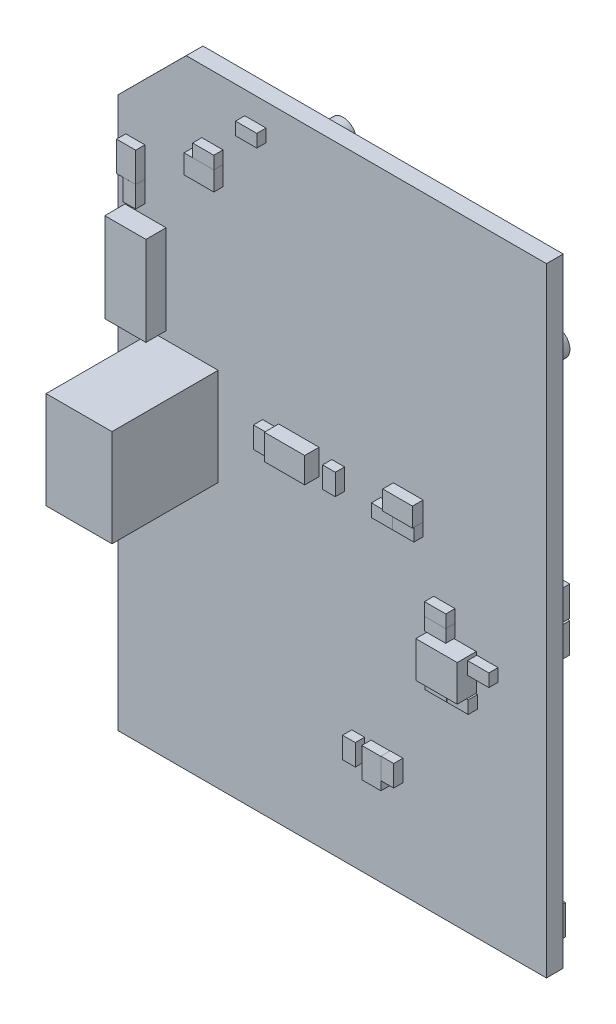
SolidWorks part; units mm, degrees
ref_plane "Plan de face" through (0, 0, 0) normal (0, 0, 1) x (1, 0, 0)
ref_plane "Plan de dessus" through (0, 0, 0) normal (0, 1, 0) x (1, 0, 0)
ref_plane "Plan de droite" through (0, 0, 0) normal (1, 0, 0) x (0, 0, -1)
sketch "Esquisse1" plane through (0, 0, 0) normal (0, 0, 1) x (1, 0, 0)
  line L0 (0, 0) -> (40.32, 0)
  line L1 (40.32, 0) -> (40.32, 58.24)
  line L2 (40.32, 58.24) -> (6.406, 58.24)
  line L3 (6.406, 58.24) -> (0, 51.854)
  line L4 (0, 51.854) -> (0, 0)
extrude "BOARD" add sketch "Esquisse1" along normal blind 1.5748 separate body
ref_plane "Plan1" through (0, 0, 1.5748) normal (0, 0, 1) x (1, 0, 0)
sketch "Esquisse2" plane through (0, 0, 0) normal (0, 0, 1) x (1, 0, 0)
  circle A0 centre (32.2039, 48.279) radius 1.25
extrude "TMR16-1" add sketch "Esquisse2" against normal blind 2.5 separate body
sketch "Esquisse3" plane through (0, 0, 0) normal (0, 0, 1) x (1, 0, 0)
  line L0 (24.4727, 4.7082) -> (27.2727, 4.7082)
  line L1 (27.2727, 4.7082) -> (27.2727, 2.9082)
  line L2 (27.2727, 2.9082) -> (24.4727, 2.9082)
  line L3 (24.4727, 2.9082) -> (24.4727, 4.7082)
extrude "C0603-1" add sketch "Esquisse3" against normal blind 0.87 separate body
sketch "Esquisse4" plane through (0, 0, 0) normal (0, 0, 1) x (1, 0, 0)
  line L0 (21.4089, 41.8009) -> (21.4089, 44.6009)
  line L1 (21.4089, 44.6009) -> (23.2089, 44.6009)
  line L2 (23.2089, 44.6009) -> (23.2089, 41.8009)
  line L3 (23.2089, 41.8009) -> (21.4089, 41.8009)
extrude "R0603-1" add sketch "Esquisse4" against normal blind 0.87 separate body
sketch "Esquisse5" plane through (0, 0, 1.5748) normal (0, 0, 1) x (1, 0, 0)
  line L0 (18.9097, 32.5678) -> (15.1097, 32.5678)
  line L1 (15.1097, 32.5678) -> (15.1097, 30.1678)
  line L2 (15.1097, 30.1678) -> (18.9097, 30.1678)
  line L3 (18.9097, 30.1678) -> (18.9097, 32.5678)
extrude "C0805-1" add sketch "Esquisse5" along normal blind 1.35 separate body
sketch "Esquisse6" plane through (0, 0, 0) normal (0, 0, 1) x (1, 0, 0)
  line L0 (12.7187, 47.5247) -> (12.7187, 44.7247)
  line L1 (12.7187, 44.7247) -> (10.9187, 44.7247)
  line L2 (10.9187, 44.7247) -> (10.9187, 47.5247)
  line L3 (10.9187, 47.5247) -> (12.7187, 47.5247)
extrude "R0603-2" add sketch "Esquisse6" against normal blind 0.87 separate body
sketch "Esquisse7" plane through (0, 0, 1.5748) normal (0, 0, 1) x (1, 0, 0)
  line L0 (9.4166, 24.9432) -> (9.4166, 34.0932)
  line L1 (9.4166, 34.0932) -> (3.2166, 34.0932)
  line L2 (3.2166, 34.0932) -> (3.2166, 24.9432)
  line L3 (3.2166, 24.9432) -> (9.4166, 24.9432)
extrude "B2B-PH-SM4-TB-1" add sketch "Esquisse7" along normal blind 10 separate body
sketch "Esquisse8" plane through (0, 0, 0) normal (0, 0, 1) x (1, 0, 0)
  line L0 (17.22, 23.0445) -> (14.42, 23.0445)
  line L1 (14.42, 23.0445) -> (14.42, 24.8445)
  line L2 (14.42, 24.8445) -> (17.22, 24.8445)
  line L3 (17.22, 24.8445) -> (17.22, 23.0445)
extrude "C0603-2" add sketch "Esquisse8" against normal blind 0.87 separate body
sketch "Esquisse9" plane through (0, 0, 0) normal (0, 0, 1) x (1, 0, 0)
  line L0 (9.9677, 30.5174) -> (9.9677, 32.5174)
  line L1 (9.9677, 32.5174) -> (11.1677, 32.5174)
  line L2 (11.1677, 32.5174) -> (11.1677, 30.5174)
  line L3 (11.1677, 30.5174) -> (9.9677, 30.5174)
extrude "C0402-1" add sketch "Esquisse9" against normal blind 0.87 separate body
sketch "Esquisse10" plane through (0, 0, 0) normal (0, 0, 1) x (1, 0, 0)
  line L0 (18.0259, 36.7794) -> (18.0259, 34.7794)
  line L1 (18.0259, 34.7794) -> (16.8259, 34.7794)
  line L2 (16.8259, 34.7794) -> (16.8259, 36.7794)
  line L3 (16.8259, 36.7794) -> (18.0259, 36.7794)
extrude "C0402-2" add sketch "Esquisse10" against normal blind 0.87 separate body
sketch "Esquisse11" plane through (0, 0, 0) normal (0, 0, 1) x (1, 0, 0)
  line L0 (36.5132, 3.569) -> (36.5132, 1.569)
  line L1 (36.5132, 1.569) -> (35.3132, 1.569)
  line L2 (35.3132, 1.569) -> (35.3132, 3.569)
  line L3 (35.3132, 3.569) -> (36.5132, 3.569)
extrude "C0402-3" add sketch "Esquisse11" against normal blind 0.87 separate body
sketch "Esquisse12" plane through (0, 0, 0) normal (0, 0, 1) x (1, 0, 0)
  line L0 (31.1602, 39.1238) -> (31.1602, 41.9238)
  line L1 (31.1602, 41.9238) -> (32.9602, 41.9238)
  line L2 (32.9602, 41.9238) -> (32.9602, 39.1238)
  line L3 (32.9602, 39.1238) -> (31.1602, 39.1238)
extrude "R0603-3" add sketch "Esquisse12" against normal blind 0.87 separate body
sketch "Esquisse13" plane through (0, 0, 0) normal (0, 0, 1) x (1, 0, 0)
  line L0 (23.2126, 47.4009) -> (23.2126, 44.6009)
  line L1 (23.2126, 44.6009) -> (21.4126, 44.6009)
  line L2 (21.4126, 44.6009) -> (21.4126, 47.4009)
  line L3 (21.4126, 47.4009) -> (23.2126, 47.4009)
extrude "R0603-4" add sketch "Esquisse13" against normal blind 0.87 separate body
sketch "Esquisse14" plane through (0, 0, 1.5748) normal (0, 0, 1) x (1, 0, 0)
  line L0 (0.64, 43.2631) -> (0.64, 34.8631)
  line L1 (0.64, 34.8631) -> (4.5139, 34.8631)
  line L2 (4.5139, 34.8631) -> (4.5139, 43.2631)
  line L3 (4.5139, 43.2631) -> (0.64, 43.2631)
extrude "PCM12SMTR-1" add sketch "Esquisse14" along normal blind 1.9 separate body
sketch "Esquisse17" plane through (0, 0, 0) normal (0, 0, 1) x (1, 0, 0)
  line L0 (26.3939, 26.7629) -> (26.3939, 24.7629)
  line L1 (26.3939, 24.7629) -> (25.1939, 24.7629)
  line L2 (25.1939, 24.7629) -> (25.1939, 26.7629)
  line L3 (25.1939, 26.7629) -> (26.3939, 26.7629)
extrude "C0402-4" add sketch "Esquisse17" against normal blind 0.87 separate body
sketch "Esquisse18" plane through (0, 0, 0) normal (0, 0, 1) x (1, 0, 0)
  line L0 (31.1409, 11.2779) -> (35.3409, 11.2779)
  line L1 (35.3409, 11.2779) -> (35.3409, 8.7779)
  line L2 (35.3409, 8.7779) -> (31.1409, 8.7779)
  line L3 (31.1409, 8.7779) -> (31.1409, 11.2779)
extrude "FC135-1" add sketch "Esquisse18" against normal blind 0.8 separate body
sketch "Esquisse19" plane through (0, 0, 0) normal (0, 0, 1) x (1, 0, 0)
  line L0 (37.8323, 19.2239) -> (35.0323, 19.2239)
  line L1 (35.0323, 19.2239) -> (35.0323, 21.0239)
  line L2 (35.0323, 21.0239) -> (37.8323, 21.0239)
  line L3 (37.8323, 21.0239) -> (37.8323, 19.2239)
extrude "C0603-3" add sketch "Esquisse19" against normal blind 0.87 separate body
sketch "Esquisse20" plane through (0, 0, 1.5748) normal (0, 0, 1) x (1, 0, 0)
  line L0 (31.8247, 18.665) -> (33.8247, 18.665)
  line L1 (33.8247, 18.665) -> (33.8247, 19.865)
  line L2 (33.8247, 19.865) -> (31.8247, 19.865)
  line L3 (31.8247, 19.865) -> (31.8247, 18.665)
extrude "C0402-5" add sketch "Esquisse20" along normal blind 0.87 separate body
sketch "Esquisse21" plane through (0, 0, 0) normal (0, 0, 1) x (1, 0, 0)
  line L0 (16.4144, 19.928) -> (16.4144, 17.928)
  line L1 (16.4144, 17.928) -> (15.2144, 17.928)
  line L2 (15.2144, 17.928) -> (15.2144, 19.928)
  line L3 (15.2144, 19.928) -> (16.4144, 19.928)
extrude "R0402-1" add sketch "Esquisse21" against normal blind 0.87 separate body
sketch "Esquisse22" plane through (0, 0, 1.5748) normal (0, 0, 1) x (1, 0, 0)
  line L0 (23.1938, 9.067) -> (23.1938, 11.067)
  line L1 (23.1938, 11.067) -> (21.9938, 11.067)
  line L2 (21.9938, 11.067) -> (21.9938, 9.067)
  line L3 (21.9938, 9.067) -> (23.1938, 9.067)
extrude "R0402-2" add sketch "Esquisse22" along normal blind 0.87 separate body
sketch "Esquisse24" plane through (0, 0, 0) normal (0, 0, 1) x (1, 0, 0)
  line L0 (16.8284, 26.8617) -> (16.8284, 24.8617)
  line L1 (16.8284, 24.8617) -> (15.6284, 24.8617)
  line L2 (15.6284, 24.8617) -> (15.6284, 26.8617)
  line L3 (15.6284, 26.8617) -> (16.8284, 26.8617)
extrude "C0402-6" add sketch "Esquisse24" against normal blind 0.87 separate body
sketch "Esquisse25" plane through (0, 0, 1.5748) normal (0, 0, 1) x (1, 0, 0)
  line L0 (31.7718, 19.8619) -> (29.7718, 19.8619)
  line L1 (29.7718, 19.8619) -> (29.7718, 18.6619)
  line L2 (29.7718, 18.6619) -> (31.7718, 18.6619)
  line L3 (31.7718, 18.6619) -> (31.7718, 19.8619)
extrude "C0402-7" add sketch "Esquisse25" along normal blind 0.87 separate body
sketch "Esquisse26" plane through (0, 0, 0) normal (0, 0, 1) x (1, 0, 0)
  line L0 (25.1939, 26.7658) -> (25.1939, 23.9658)
  line L1 (25.1939, 23.9658) -> (23.3939, 23.9658)
  line L2 (23.3939, 23.9658) -> (23.3939, 26.7658)
  line L3 (23.3939, 26.7658) -> (25.1939, 26.7658)
extrude "C0603-4" add sketch "Esquisse26" against normal blind 0.87 separate body
sketch "Esquisse27" plane through (0, 0, 1.5748) normal (0, 0, 1) x (1, 0, 0)
  line L0 (7.8734, 51.0902) -> (9.8734, 51.0902)
  line L1 (9.8734, 51.0902) -> (9.8734, 52.2902)
  line L2 (9.8734, 52.2902) -> (7.8734, 52.2902)
  line L3 (7.8734, 52.2902) -> (7.8734, 51.0902)
extrude "C0402-8" add sketch "Esquisse27" along normal blind 0.87 separate body
sketch "Esquisse28" plane through (0, 0, 0) normal (0, 0, 1) x (1, 0, 0)
  line L0 (29.9409, 8.7816) -> (29.9409, 10.7816)
  line L1 (29.9409, 10.7816) -> (31.1409, 10.7816)
  line L2 (31.1409, 10.7816) -> (31.1409, 8.7816)
  line L3 (31.1409, 8.7816) -> (29.9409, 8.7816)
extrude "C0402-9" add sketch "Esquisse28" against normal blind 0.87 separate body
sketch "Esquisse29" plane through (0, 0, 0) normal (0, 0, 1) x (1, 0, 0)
  line L0 (30.2532, 33.9315) -> (33.0532, 33.9315)
  line L1 (33.0532, 33.9315) -> (33.0532, 32.1315)
  line L2 (33.0532, 32.1315) -> (30.2532, 32.1315)
  line L3 (30.2532, 32.1315) -> (30.2532, 33.9315)
extrude "R0603-5" add sketch "Esquisse29" against normal blind 0.87 separate body
sketch "Esquisse30" plane through (0, 0, 0) normal (0, 0, 1) x (1, 0, 0)
  circle A0 centre (37.2015, 48.2753) radius 1.25
extrude "TMR16-2" add sketch "Esquisse30" against normal blind 2.5 separate body
sketch "Esquisse31" plane through (0, 0, 0) normal (0, 0, 1) x (1, 0, 0)
  line L0 (30.266, 27.6789) -> (30.266, 29.6789)
  line L1 (30.266, 29.6789) -> (31.466, 29.6789)
  line L2 (31.466, 29.6789) -> (31.466, 27.6789)
  line L3 (31.466, 27.6789) -> (30.266, 27.6789)
extrude "C0402-10" add sketch "Esquisse31" against normal blind 0.87 separate body
sketch "Esquisse33" plane through (0, 0, 0) normal (0, 0, 1) x (1, 0, 0)
  line L0 (33.1436, 12.4818) -> (35.1436, 12.4818)
  line L1 (35.1436, 12.4818) -> (35.1436, 11.2818)
  line L2 (35.1436, 11.2818) -> (33.1436, 11.2818)
  line L3 (33.1436, 11.2818) -> (33.1436, 12.4818)
extrude "C0402-11" add sketch "Esquisse33" against normal blind 0.87 separate body
sketch "Esquisse34" plane through (0, 0, 0) normal (0, 0, 1) x (1, 0, 0)
  line L0 (38.6703, 42.6598) -> (38.6703, 40.6598)
  line L1 (38.6703, 40.6598) -> (37.4703, 40.6598)
  line L2 (37.4703, 40.6598) -> (37.4703, 42.6598)
  line L3 (37.4703, 42.6598) -> (38.6703, 42.6598)
extrude "C0402-12" add sketch "Esquisse34" against normal blind 0.87 separate body
sketch "Esquisse36" plane through (0, 0, 0) normal (0, 0, 1) x (1, 0, 0)
  line L0 (38.6602, 38.2995) -> (38.6602, 36.2995)
  line L1 (38.6602, 36.2995) -> (37.4602, 36.2995)
  line L2 (37.4602, 36.2995) -> (37.4602, 38.2995)
  line L3 (37.4602, 38.2995) -> (38.6602, 38.2995)
extrude "R0402-3" add sketch "Esquisse36" against normal blind 0.87 separate body
sketch "Esquisse37" plane through (0, 0, 0) normal (0, 0, 1) x (1, 0, 0)
  line L0 (23.2036, 40.9713) -> (23.2036, 38.9713)
  line L1 (23.2036, 38.9713) -> (22.0036, 38.9713)
  line L2 (22.0036, 38.9713) -> (22.0036, 40.9713)
  line L3 (22.0036, 40.9713) -> (23.2036, 40.9713)
extrude "R0402-4" add sketch "Esquisse37" against normal blind 0.87 separate body
sketch "Esquisse38" plane through (0, 0, 1.5748) normal (0, 0, 1) x (1, 0, 0)
  line L0 (25.907, 31.3651) -> (28.707, 31.3651)
  line L1 (28.707, 31.3651) -> (28.707, 33.1651)
  line L2 (28.707, 33.1651) -> (25.907, 33.1651)
  line L3 (25.907, 33.1651) -> (25.907, 31.3651)
extrude "D0603-1" add sketch "Esquisse38" along normal blind 1 separate body
sketch "Esquisse39" plane through (0, 0, 0) normal (0, 0, 1) x (1, 0, 0)
  line L0 (33.3683, 1.6523) -> (34.3683, 1.6523)
  line L1 (34.3683, 1.6523) -> (34.3683, 0.6523)
  line L2 (34.3683, 0.6523) -> (33.3683, 0.6523)
  line L3 (33.3683, 0.6523) -> (33.3683, 1.6523)
extrude "PAD_1x1-1" add sketch "Esquisse39" against normal blind 2.54 separate body
sketch "Esquisse40" plane through (0, 0, 1.5748) normal (0, 0, 1) x (1, 0, 0)
  line L0 (33.7636, 21.8308) -> (35.7636, 21.8308)
  line L1 (35.7636, 21.8308) -> (35.7636, 23.0308)
  line L2 (35.7636, 23.0308) -> (33.7636, 23.0308)
  line L3 (33.7636, 23.0308) -> (33.7636, 21.8308)
extrude "C0402-13" add sketch "Esquisse40" along normal blind 0.87 separate body
sketch "Esquisse41" plane through (0, 0, 1.5748) normal (0, 0, 1) x (1, 0, 0)
  line L0 (26.7069, 30.1651) -> (28.7069, 30.1651)
  line L1 (28.7069, 30.1651) -> (28.7069, 31.3651)
  line L2 (28.7069, 31.3651) -> (26.7069, 31.3651)
  line L3 (26.7069, 31.3651) -> (26.7069, 30.1651)
extrude "R0402-5" add sketch "Esquisse41" along normal blind 0.87 separate body
sketch "Esquisse42" plane through (0, 0, 1.5748) normal (0, 0, 1) x (1, 0, 0)
  line L0 (31.7099, 24.6143) -> (29.7099, 24.6143)
  line L1 (29.7099, 24.6143) -> (29.7099, 23.4143)
  line L2 (29.7099, 23.4143) -> (31.7099, 23.4143)
  line L3 (31.7099, 23.4143) -> (31.7099, 24.6143)
extrude "C0402-14" add sketch "Esquisse42" along normal blind 0.87 separate body
sketch "Esquisse43" plane through (0, 0, 0) normal (0, 0, 1) x (1, 0, 0)
  line L0 (17.2288, 45.591) -> (17.2288, 47.591)
  line L1 (17.2288, 47.591) -> (18.4288, 47.591)
  line L2 (18.4288, 47.591) -> (18.4288, 45.591)
  line L3 (18.4288, 45.591) -> (17.2288, 45.591)
extrude "R0402-6" add sketch "Esquisse43" against normal blind 0.87 separate body
sketch "Esquisse44" plane through (0, 0, 1.5748) normal (0, 0, 1) x (1, 0, 0)
  line L0 (0.7203, 49.0243) -> (0.7203, 46.2243)
  line L1 (0.7203, 46.2243) -> (2.5203, 46.2243)
  line L2 (2.5203, 46.2243) -> (2.5203, 49.0243)
  line L3 (2.5203, 49.0243) -> (0.7203, 49.0243)
extrude "C0603-5" add sketch "Esquisse44" along normal blind 0.87 separate body
sketch "Esquisse45" plane through (0, 0, 0) normal (0, 0, 1) x (1, 0, 0)
  line L0 (23.2977, 35.9913) -> (26.0977, 35.9913)
  line L1 (26.0977, 35.9913) -> (26.0977, 34.1913)
  line L2 (26.0977, 34.1913) -> (23.2977, 34.1913)
  line L3 (23.2977, 34.1913) -> (23.2977, 35.9913)
extrude "R0603-6" add sketch "Esquisse45" against normal blind 0.87 separate body
sketch "Esquisse46" plane through (0, 0, 0) normal (0, 0, 1) x (1, 0, 0)
  line L0 (10.0607, 36.7556) -> (12.8607, 36.7556)
  line L1 (12.8607, 36.7556) -> (12.8607, 34.9556)
  line L2 (12.8607, 34.9556) -> (10.0607, 34.9556)
  line L3 (10.0607, 34.9556) -> (10.0607, 36.7556)
extrude "R0603-7" add sketch "Esquisse46" against normal blind 0.87 separate body
sketch "Esquisse47" plane through (0, 0, 0) normal (0, 0, 1) x (1, 0, 0)
  line L0 (28.9167, 40.9735) -> (28.9167, 38.9735)
  line L1 (28.9167, 38.9735) -> (27.7167, 38.9735)
  line L2 (27.7167, 38.9735) -> (27.7167, 40.9735)
  line L3 (27.7167, 40.9735) -> (28.9167, 40.9735)
extrude "R0402-7" add sketch "Esquisse47" against normal blind 0.87 separate body
sketch "Esquisse48" plane through (0, 0, 0) normal (0, 0, 1) x (1, 0, 0)
  line L0 (28.4582, 27.7214) -> (28.4582, 30.5214)
  line L1 (28.4582, 30.5214) -> (30.2582, 30.5214)
  line L2 (30.2582, 30.5214) -> (30.2582, 27.7214)
  line L3 (30.2582, 27.7214) -> (28.4582, 27.7214)
extrude "C0603-6" add sketch "Esquisse48" against normal blind 0.87 separate body
sketch "Esquisse49" plane through (0, 0, 0) normal (0, 0, 1) x (1, 0, 0)
  line L0 (18.3486, 51.2303) -> (18.3486, 54.0303)
  line L1 (18.3486, 54.0303) -> (20.1486, 54.0303)
  line L2 (20.1486, 54.0303) -> (20.1486, 51.2303)
  line L3 (20.1486, 51.2303) -> (18.3486, 51.2303)
extrude "C0603-7" add sketch "Esquisse49" against normal blind 0.87 separate body
sketch "Esquisse52" plane through (0, 0, 0) normal (0, 0, 1) x (1, 0, 0)
  line L0 (28.4532, 30.5214) -> (28.4532, 33.3214)
  line L1 (28.4532, 33.3214) -> (30.2532, 33.3214)
  line L2 (30.2532, 33.3214) -> (30.2532, 30.5214)
  line L3 (30.2532, 30.5214) -> (28.4532, 30.5214)
extrude "C0603-8" add sketch "Esquisse52" against normal blind 0.87 separate body
sketch "Esquisse53" plane through (0, 0, 0) normal (0, 0, 1) x (1, 0, 0)
  line L0 (12.6415, 15.1419) -> (12.6415, 13.1419)
  line L1 (12.6415, 13.1419) -> (11.4415, 13.1419)
  line L2 (11.4415, 13.1419) -> (11.4415, 15.1419)
  line L3 (11.4415, 15.1419) -> (12.6415, 15.1419)
extrude "C0402-15" add sketch "Esquisse53" against normal blind 0.87 separate body
sketch "Esquisse54" plane through (0, 0, 0) normal (0, 0, 1) x (1, 0, 0)
  line L0 (14.428, 17.8103) -> (16.428, 17.8103)
  line L1 (16.428, 17.8103) -> (16.428, 16.6103)
  line L2 (16.428, 16.6103) -> (14.428, 16.6103)
  line L3 (14.428, 16.6103) -> (14.428, 17.8103)
extrude "C0402-16" add sketch "Esquisse54" against normal blind 0.87 separate body
sketch "Esquisse55" plane through (0, 0, 1.5748) normal (0, 0, 1) x (1, 0, 0)
  line L0 (33.7164, 19.9169) -> (33.7164, 23.3169)
  line L1 (33.7164, 23.3169) -> (29.8164, 23.3169)
  line L2 (29.8164, 23.3169) -> (29.8164, 19.9169)
  line L3 (29.8164, 19.9169) -> (33.7164, 19.9169)
extrude "NX2520-1" add sketch "Esquisse55" along normal blind 1.8 separate body
sketch "Esquisse56" plane through (0, 0, 0) normal (0, 0, 1) x (1, 0, 0)
  line L0 (37.6786, 21.5996) -> (35.6786, 21.5996)
  line L1 (35.6786, 21.5996) -> (35.6786, 22.7996)
  line L2 (35.6786, 22.7996) -> (37.6786, 22.7996)
  line L3 (37.6786, 22.7996) -> (37.6786, 21.5996)
extrude "C0402-17" add sketch "Esquisse56" against normal blind 0.87 separate body
sketch "Esquisse57" plane through (0, 0, 0) normal (0, 0, 1) x (1, 0, 0)
  line L0 (17.9677, 27.8144) -> (17.9677, 30.6144)
  line L1 (17.9677, 30.6144) -> (19.7677, 30.6144)
  line L2 (19.7677, 30.6144) -> (19.7677, 27.8144)
  line L3 (19.7677, 27.8144) -> (17.9677, 27.8144)
extrude "C0603-9" add sketch "Esquisse57" against normal blind 0.87 separate body
sketch "Esquisse59" plane through (0, 0, 0) normal (0, 0, 1) x (1, 0, 0)
  line L0 (18.4233, 41.0792) -> (18.4233, 39.0792)
  line L1 (18.4233, 39.0792) -> (17.2233, 39.0792)
  line L2 (17.2233, 39.0792) -> (17.2233, 41.0792)
  line L3 (17.2233, 41.0792) -> (18.4233, 41.0792)
extrude "R0402-8" add sketch "Esquisse59" against normal blind 0.87 separate body
sketch "Esquisse60" plane through (0, 0, 0) normal (0, 0, 1) x (1, 0, 0)
  line L0 (28.5034, 36.6137) -> (28.5034, 34.6137)
  line L1 (28.5034, 34.6137) -> (27.3034, 34.6137)
  line L2 (27.3034, 34.6137) -> (27.3034, 36.6137)
  line L3 (27.3034, 36.6137) -> (28.5034, 36.6137)
extrude "C0402-18" add sketch "Esquisse60" against normal blind 0.87 separate body
sketch "Esquisse61" plane through (0, 0, 0) normal (0, 0, 1) x (1, 0, 0)
  line L0 (28.4922, 4.2513) -> (28.4922, 2.2513)
  line L1 (28.4922, 2.2513) -> (27.2922, 2.2513)
  line L2 (27.2922, 2.2513) -> (27.2922, 4.2513)
  line L3 (27.2922, 4.2513) -> (28.4922, 4.2513)
extrude "C0402-19" add sketch "Esquisse61" against normal blind 0.87 separate body
sketch "Esquisse63" plane through (0, 0, 0) normal (0, 0, 1) x (1, 0, 0)
  line L0 (12.8704, 36.123) -> (15.6704, 36.123)
  line L1 (15.6704, 36.123) -> (15.6704, 34.323)
  line L2 (15.6704, 34.323) -> (12.8704, 34.323)
  line L3 (12.8704, 34.323) -> (12.8704, 36.123)
extrude "R0603-8" add sketch "Esquisse63" against normal blind 0.87 separate body
sketch "Esquisse64" plane through (0, 0, 0) normal (0, 0, 1) x (1, 0, 0)
  line L0 (20.0201, 20.1616) -> (18.0201, 20.1616)
  line L1 (18.0201, 20.1616) -> (18.0201, 21.3616)
  line L2 (18.0201, 21.3616) -> (20.0201, 21.3616)
  line L3 (20.0201, 21.3616) -> (20.0201, 20.1616)
extrude "C0402-20" add sketch "Esquisse64" against normal blind 0.87 separate body
sketch "Esquisse65" plane through (0, 0, 1.5748) normal (0, 0, 1) x (1, 0, 0)
  line L0 (20.1126, 32.1652) -> (20.1126, 30.1652)
  line L1 (20.1126, 30.1652) -> (21.3126, 30.1652)
  line L2 (21.3126, 30.1652) -> (21.3126, 32.1652)
  line L3 (21.3126, 32.1652) -> (20.1126, 32.1652)
extrude "R0402-9" add sketch "Esquisse65" along normal blind 0.87 separate body
sketch "Esquisse66" plane through (0, 0, 0) normal (0, 0, 1) x (1, 0, 0)
  line L0 (37.4717, 42.6598) -> (37.4717, 44.6598)
  line L1 (37.4717, 44.6598) -> (38.6717, 44.6598)
  line L2 (38.6717, 44.6598) -> (38.6717, 42.6598)
  line L3 (38.6717, 42.6598) -> (37.4717, 42.6598)
extrude "R0402-10" add sketch "Esquisse66" against normal blind 0.87 separate body
sketch "Esquisse69" plane through (0, 0, 0) normal (0, 0, 1) x (1, 0, 0)
  line L0 (31.9877, 1.64) -> (32.9877, 1.64)
  line L1 (32.9877, 1.64) -> (32.9877, 0.64)
  line L2 (32.9877, 0.64) -> (31.9877, 0.64)
  line L3 (31.9877, 0.64) -> (31.9877, 1.64)
extrude "PAD_1x1-2" add sketch "Esquisse69" against normal blind 2.54 separate body
sketch "Esquisse70" plane through (0, 0, 0) normal (0, 0, 1) x (1, 0, 0)
  line L0 (32.9602, 44.7238) -> (32.9602, 41.9238)
  line L1 (32.9602, 41.9238) -> (31.1602, 41.9238)
  line L2 (31.1602, 41.9238) -> (31.1602, 44.7238)
  line L3 (31.1602, 44.7238) -> (32.9602, 44.7238)
extrude "R0603-9" add sketch "Esquisse70" against normal blind 0.87 separate body
sketch "Esquisse72" plane through (0, 0, 0) normal (0, 0, 1) x (1, 0, 0)
  line L0 (37.6897, 22.8247) -> (35.6897, 22.8247)
  line L1 (35.6897, 22.8247) -> (35.6897, 24.0247)
  line L2 (35.6897, 24.0247) -> (37.6897, 24.0247)
  line L3 (37.6897, 24.0247) -> (37.6897, 22.8247)
extrude "C0402-21" add sketch "Esquisse72" against normal blind 0.87 separate body
sketch "Esquisse73" plane through (0, 0, 0) normal (0, 0, 1) x (1, 0, 0)
  line L0 (38.266, 27.9786) -> (38.266, 30.7786)
  line L1 (38.266, 30.7786) -> (40.066, 30.7786)
  line L2 (40.066, 30.7786) -> (40.066, 27.9786)
  line L3 (40.066, 27.9786) -> (38.266, 27.9786)
extrude "C0603-10" add sketch "Esquisse73" against normal blind 0.87 separate body
sketch "Esquisse74" plane through (0, 0, 0) normal (0, 0, 1) x (1, 0, 0)
  line L0 (36.5201, 5.6764) -> (36.5201, 3.6764)
  line L1 (36.5201, 3.6764) -> (35.3201, 3.6764)
  line L2 (35.3201, 3.6764) -> (35.3201, 5.6764)
  line L3 (35.3201, 5.6764) -> (36.5201, 5.6764)
extrude "R0402-11" add sketch "Esquisse74" against normal blind 0.87 separate body
sketch "Esquisse76" plane through (0, 0, 0) normal (0, 0, 1) x (1, 0, 0)
  line L0 (38.266, 24.9805) -> (38.266, 27.7805)
  line L1 (38.266, 27.7805) -> (40.066, 27.7805)
  line L2 (40.066, 27.7805) -> (40.066, 24.9805)
  line L3 (40.066, 24.9805) -> (38.266, 24.9805)
extrude "C0603-11" add sketch "Esquisse76" against normal blind 0.87 separate body
sketch "Esquisse77" plane through (0, 0, 0) normal (0, 0, 1) x (1, 0, 0)
  line L0 (10.7187, 48.7247) -> (12.7187, 48.7247)
  line L1 (12.7187, 48.7247) -> (12.7187, 47.5247)
  line L2 (12.7187, 47.5247) -> (10.7187, 47.5247)
  line L3 (10.7187, 47.5247) -> (10.7187, 48.7247)
extrude "C0402-22" add sketch "Esquisse77" against normal blind 0.87 separate body
sketch "Esquisse78" plane through (0, 0, 0) normal (0, 0, 1) x (1, 0, 0)
  line L0 (18.4288, 45.591) -> (18.4288, 43.591)
  line L1 (18.4288, 43.591) -> (17.2288, 43.591)
  line L2 (17.2288, 43.591) -> (17.2288, 45.591)
  line L3 (17.2288, 45.591) -> (18.4288, 45.591)
extrude "C0402-23" add sketch "Esquisse78" against normal blind 0.87 separate body
sketch "Esquisse80" plane through (0, 0, 0) normal (0, 0, 1) x (1, 0, 0)
  line L0 (39.3369, 4.4834) -> (36.5369, 4.4834)
  line L1 (36.5369, 4.4834) -> (36.5369, 6.2834)
  line L2 (36.5369, 6.2834) -> (39.3369, 6.2834)
  line L3 (39.3369, 6.2834) -> (39.3369, 4.4834)
extrude "R0603-10" add sketch "Esquisse80" against normal blind 0.87 separate body
sketch "Esquisse81" plane through (0, 0, 0) normal (0, 0, 1) x (1, 0, 0)
  circle A0 centre (17.0986, 50.277) radius 1.25
extrude "TMR16-3" add sketch "Esquisse81" against normal blind 2.5 separate body
sketch "Esquisse82" plane through (0, 0, 0) normal (0, 0, 1) x (1, 0, 0)
  line L0 (26.5132, 8.1312) -> (28.5132, 8.1312)
  line L1 (28.5132, 8.1312) -> (28.5132, 6.9312)
  line L2 (28.5132, 6.9312) -> (26.5132, 6.9312)
  line L3 (26.5132, 6.9312) -> (26.5132, 8.1312)
extrude "C0402-24" add sketch "Esquisse82" against normal blind 0.87 separate body
sketch "Esquisse85" plane through (0, 0, 1.5748) normal (0, 0, 1) x (1, 0, 0)
  line L0 (26.808, 9.1651) -> (26.808, 11.1651)
  line L1 (26.808, 11.1651) -> (25.608, 11.1651)
  line L2 (25.608, 11.1651) -> (25.608, 9.1651)
  line L3 (25.608, 9.1651) -> (26.808, 9.1651)
extrude "C0402-25" add sketch "Esquisse85" along normal blind 0.87 separate body
sketch "Esquisse86" plane through (0, 0, 0) normal (0, 0, 1) x (1, 0, 0)
  line L0 (29.7581, 8.8221) -> (26.3581, 8.8221)
  line L1 (26.3581, 8.8221) -> (26.3581, 12.7221)
  line L2 (26.3581, 12.7221) -> (29.7581, 12.7221)
  line L3 (29.7581, 12.7221) -> (29.7581, 8.8221)
extrude "NX2520-2" add sketch "Esquisse86" against normal blind 1.8 separate body
sketch "Esquisse88" plane through (0, 0, 0) normal (0, 0, 1) x (1, 0, 0)
  line L0 (22.7677, 17.3617) -> (22.7677, 20.1617)
  line L1 (22.7677, 20.1617) -> (24.5677, 20.1617)
  line L2 (24.5677, 20.1617) -> (24.5677, 17.3617)
  line L3 (24.5677, 17.3617) -> (22.7677, 17.3617)
extrude "C0603-12" add sketch "Esquisse88" against normal blind 0.87 separate body
sketch "Esquisse89" plane through (0, 0, 0) normal (0, 0, 1) x (1, 0, 0)
  line L0 (33.0532, 33.3221) -> (35.8532, 33.3221)
  line L1 (35.8532, 33.3221) -> (35.8532, 31.5221)
  line L2 (35.8532, 31.5221) -> (33.0532, 31.5221)
  line L3 (33.0532, 31.5221) -> (33.0532, 33.3221)
extrude "R0603-11" add sketch "Esquisse89" against normal blind 0.87 separate body
sketch "Esquisse90" plane through (0, 0, 0) normal (0, 0, 1) x (1, 0, 0)
  line L0 (21.2114, 48.6009) -> (23.2114, 48.6009)
  line L1 (23.2114, 48.6009) -> (23.2114, 47.4009)
  line L2 (23.2114, 47.4009) -> (21.2114, 47.4009)
  line L3 (21.2114, 47.4009) -> (21.2114, 48.6009)
extrude "C0402-26" add sketch "Esquisse90" against normal blind 0.87 separate body
sketch "Esquisse91" plane through (0, 0, 0) normal (0, 0, 1) x (1, 0, 0)
  line L0 (30.9904, 13.5763) -> (30.9904, 11.5763)
  line L1 (30.9904, 11.5763) -> (29.7904, 11.5763)
  line L2 (29.7904, 11.5763) -> (29.7904, 13.5763)
  line L3 (29.7904, 13.5763) -> (30.9904, 13.5763)
extrude "C0402-27" add sketch "Esquisse91" against normal blind 0.87 separate body
sketch "Esquisse92" plane through (0, 0, 1.5748) normal (0, 0, 1) x (1, 0, 0)
  line L0 (26.7052, 31.3651) -> (24.7052, 31.3651)
  line L1 (24.7052, 31.3651) -> (24.7052, 30.1651)
  line L2 (24.7052, 30.1651) -> (26.7052, 30.1651)
  line L3 (26.7052, 30.1651) -> (26.7052, 31.3651)
extrude "C0402-28" add sketch "Esquisse92" along normal blind 0.87 separate body
sketch "Esquisse93" plane through (0, 0, 0) normal (0, 0, 1) x (1, 0, 0)
  line L0 (22.1939, 24.7606) -> (22.1939, 26.7606)
  line L1 (22.1939, 26.7606) -> (23.3939, 26.7606)
  line L2 (23.3939, 26.7606) -> (23.3939, 24.7606)
  line L3 (23.3939, 24.7606) -> (22.1939, 24.7606)
extrude "R0402-12" add sketch "Esquisse93" against normal blind 0.87 separate body
sketch "Esquisse94" plane through (0, 0, 0) normal (0, 0, 1) x (1, 0, 0)
  line L0 (28.9138, 45.487) -> (28.9138, 43.487)
  line L1 (28.9138, 43.487) -> (27.7138, 43.487)
  line L2 (27.7138, 43.487) -> (27.7138, 45.487)
  line L3 (27.7138, 45.487) -> (28.9138, 45.487)
extrude "C0402-29" add sketch "Esquisse94" against normal blind 0.87 separate body
sketch "Esquisse95" plane through (0, 0, 0) normal (0, 0, 1) x (1, 0, 0)
  line L0 (6.8995, 16.8472) -> (10.6995, 16.8472)
  line L1 (10.6995, 16.8472) -> (10.6995, 14.4472)
  line L2 (10.6995, 14.4472) -> (6.8995, 14.4472)
  line L3 (6.8995, 14.4472) -> (6.8995, 16.8472)
extrude "C0805-2" add sketch "Esquisse95" against normal blind 1.35 separate body
sketch "Esquisse96" plane through (0, 0, 0) normal (0, 0, 1) x (1, 0, 0)
  line L0 (20.4914, 36.5874) -> (23.2914, 36.5874)
  line L1 (23.2914, 36.5874) -> (23.2914, 34.7874)
  line L2 (23.2914, 34.7874) -> (20.4914, 34.7874)
  line L3 (20.4914, 34.7874) -> (20.4914, 36.5874)
extrude "R0603-12" add sketch "Esquisse96" against normal blind 0.87 separate body
sketch "Esquisse97" plane through (0, 0, 0) normal (0, 0, 1) x (1, 0, 0)
  line L0 (23.1885, 2.8155) -> (23.1885, 0.8155)
  line L1 (23.1885, 0.8155) -> (21.9885, 0.8155)
  line L2 (21.9885, 0.8155) -> (21.9885, 2.8155)
  line L3 (21.9885, 2.8155) -> (23.1885, 2.8155)
extrude "C0402-30" add sketch "Esquisse97" against normal blind 0.87 separate body
sketch "Esquisse99" plane through (0, 0, 0) normal (0, 0, 1) x (1, 0, 0)
  line L0 (37.7446, 1.672) -> (37.7446, 4.472)
  line L1 (37.7446, 4.472) -> (39.5446, 4.472)
  line L2 (39.5446, 4.472) -> (39.5446, 1.672)
  line L3 (39.5446, 1.672) -> (37.7446, 1.672)
extrude "D0603-2" add sketch "Esquisse99" against normal blind 1 separate body
sketch "Esquisse100" plane through (0, 0, 0) normal (0, 0, 1) x (1, 0, 0)
  line L0 (5.454, 0.254) -> (0.254, 0.254)
  line L1 (0.254, 0.254) -> (0.254, 3.854)
  line L2 (0.254, 3.854) -> (5.454, 3.854)
  line L3 (5.454, 3.854) -> (5.454, 0.254)
extrude "2450AT18A100-1" add sketch "Esquisse100" against normal blind 1.3 separate body
sketch "Esquisse101" plane through (0, 0, 1.5748) normal (0, 0, 1) x (1, 0, 0)
  line L0 (13.6077, 32.1678) -> (13.6077, 30.1678)
  line L1 (13.6077, 30.1678) -> (14.8077, 30.1678)
  line L2 (14.8077, 30.1678) -> (14.8077, 32.1678)
  line L3 (14.8077, 32.1678) -> (13.6077, 32.1678)
extrude "C0402-31" add sketch "Esquisse101" along normal blind 0.87 separate body
sketch "Esquisse102" plane through (0, 0, 0) normal (0, 0, 1) x (1, 0, 0)
  line L0 (10.9187, 41.9247) -> (10.9187, 44.7247)
  line L1 (10.9187, 44.7247) -> (12.7187, 44.7247)
  line L2 (12.7187, 44.7247) -> (12.7187, 41.9247)
  line L3 (12.7187, 41.9247) -> (10.9187, 41.9247)
extrude "R0603-13" add sketch "Esquisse102" against normal blind 0.87 separate body
sketch "Esquisse104" plane through (0, 0, 0) normal (0, 0, 1) x (1, 0, 0)
  circle A0 centre (17.1015, 55.2803) radius 1.25
extrude "TMR16-4" add sketch "Esquisse104" against normal blind 2.5 separate body
sketch "Esquisse105" plane through (0, 0, 0) normal (0, 0, 1) x (1, 0, 0)
  line L0 (15.6284, 26.8629) -> (15.6284, 24.8629)
  line L1 (15.6284, 24.8629) -> (14.4284, 24.8629)
  line L2 (14.4284, 24.8629) -> (14.4284, 26.8629)
  line L3 (14.4284, 26.8629) -> (15.6284, 26.8629)
extrude "C0402-32" add sketch "Esquisse105" against normal blind 0.87 separate body
sketch "Esquisse106" plane through (0, 0, 0) normal (0, 0, 1) x (1, 0, 0)
  line L0 (23.3594, 51.6851) -> (26.1594, 51.6851)
  line L1 (26.1594, 51.6851) -> (26.1594, 49.8851)
  line L2 (26.1594, 49.8851) -> (23.3594, 49.8851)
  line L3 (23.3594, 49.8851) -> (23.3594, 51.6851)
extrude "C0603-13" add sketch "Esquisse106" against normal blind 0.87 separate body
sketch "Esquisse107" plane through (0, 0, 0) normal (0, 0, 1) x (1, 0, 0)
  line L0 (37.7409, 12.0271) -> (37.7409, 8.2271)
  line L1 (37.7409, 8.2271) -> (35.3409, 8.2271)
  line L2 (35.3409, 8.2271) -> (35.3409, 12.0271)
  line L3 (35.3409, 12.0271) -> (37.7409, 12.0271)
extrude "C0805-3" add sketch "Esquisse107" against normal blind 1.35 separate body
sketch "Esquisse108" plane through (0, 0, 0) normal (0, 0, 1) x (1, 0, 0)
  line L0 (12.7187, 41.0832) -> (12.7187, 39.0832)
  line L1 (12.7187, 39.0832) -> (11.5187, 39.0832)
  line L2 (11.5187, 39.0832) -> (11.5187, 41.0832)
  line L3 (11.5187, 41.0832) -> (12.7187, 41.0832)
extrude "R0402-13" add sketch "Esquisse108" against normal blind 0.87 separate body
sketch "Esquisse109" plane through (0, 0, 0) normal (0, 0, 1) x (1, 0, 0)
  line L0 (32.4682, 20.3596) -> (34.4682, 20.3596)
  line L1 (34.4682, 20.3596) -> (34.4682, 19.1596)
  line L2 (34.4682, 19.1596) -> (32.4682, 19.1596)
  line L3 (32.4682, 19.1596) -> (32.4682, 20.3596)
extrude "R0402-14" add sketch "Esquisse109" against normal blind 0.87 separate body
sketch "Esquisse110" plane through (0, 0, 0) normal (0, 0, 1) x (1, 0, 0)
  line L0 (27.724, 45.487) -> (27.724, 47.487)
  line L1 (27.724, 47.487) -> (28.924, 47.487)
  line L2 (28.924, 47.487) -> (28.924, 45.487)
  line L3 (28.924, 45.487) -> (27.724, 45.487)
extrude "R0402-15" add sketch "Esquisse110" against normal blind 0.87 separate body
sketch "Esquisse111" plane through (0, 0, 0) normal (0, 0, 1) x (1, 0, 0)
  line L0 (15.5328, 22.3734) -> (17.5328, 22.3734)
  line L1 (17.5328, 22.3734) -> (17.5328, 21.1734)
  line L2 (17.5328, 21.1734) -> (15.5328, 21.1734)
  line L3 (15.5328, 21.1734) -> (15.5328, 22.3734)
extrude "R0402-16" add sketch "Esquisse111" against normal blind 0.87 separate body
sketch "Esquisse114" plane through (0, 0, 1.5748) normal (0, 0, 1) x (1, 0, 0)
  line L0 (31.7099, 25.8143) -> (29.7099, 25.8143)
  line L1 (29.7099, 25.8143) -> (29.7099, 24.6143)
  line L2 (29.7099, 24.6143) -> (31.7099, 24.6143)
  line L3 (31.7099, 24.6143) -> (31.7099, 25.8143)
extrude "C0402-33" add sketch "Esquisse114" along normal blind 0.87 separate body
sketch "Esquisse115" plane through (0, 0, 0) normal (0, 0, 1) x (1, 0, 0)
  line L0 (25.0988, 8.426) -> (25.0988, 10.426)
  line L1 (25.0988, 10.426) -> (26.2988, 10.426)
  line L2 (26.2988, 10.426) -> (26.2988, 8.426)
  line L3 (26.2988, 8.426) -> (25.0988, 8.426)
extrude "C0402-34" add sketch "Esquisse115" against normal blind 0.87 separate body
sketch "Esquisse116" plane through (0, 0, 0) normal (0, 0, 1) x (1, 0, 0)
  line L0 (35.509, 48.7247) -> (35.509, 45.9247)
  line L1 (35.509, 45.9247) -> (33.709, 45.9247)
  line L2 (33.709, 45.9247) -> (33.709, 48.7247)
  line L3 (33.709, 48.7247) -> (35.509, 48.7247)
extrude "C0603-14" add sketch "Esquisse116" against normal blind 0.87 separate body
sketch "Esquisse117" plane through (0, 0, 1.5748) normal (0, 0, 1) x (1, 0, 0)
  line L0 (2.5203, 44.224) -> (2.5203, 46.224)
  line L1 (2.5203, 46.224) -> (1.3203, 46.224)
  line L2 (1.3203, 46.224) -> (1.3203, 44.224)
  line L3 (1.3203, 44.224) -> (2.5203, 44.224)
extrude "C0402-35" add sketch "Esquisse117" along normal blind 0.87 separate body
sketch "Esquisse118" plane through (0, 0, 0) normal (0, 0, 1) x (1, 0, 0)
  circle A0 centre (27.2542, 52.9069) radius 1.25
extrude "TMR16-5" add sketch "Esquisse118" against normal blind 2.5 separate body
sketch "Esquisse119" plane through (0, 0, 1.5748) normal (0, 0, 1) x (1, 0, 0)
  line L0 (11.9216, 54.8976) -> (13.9216, 54.8976)
  line L1 (13.9216, 54.8976) -> (13.9216, 56.0976)
  line L2 (13.9216, 56.0976) -> (11.9216, 56.0976)
  line L3 (11.9216, 56.0976) -> (11.9216, 54.8976)
extrude "C0402-36" add sketch "Esquisse119" along normal blind 0.87 separate body
sketch "Esquisse120" plane through (0, 0, 0) normal (0, 0, 1) x (1, 0, 0)
  line L0 (11.5856, 25.7436) -> (14.3856, 25.7436)
  line L1 (14.3856, 25.7436) -> (14.3856, 23.9436)
  line L2 (14.3856, 23.9436) -> (11.5856, 23.9436)
  line L3 (11.5856, 23.9436) -> (11.5856, 25.7436)
extrude "C0603-15" add sketch "Esquisse120" against normal blind 0.87 separate body
sketch "Esquisse122" plane through (0, 0, 0) normal (0, 0, 1) x (1, 0, 0)
  line L0 (38.2617, 33.9504) -> (38.2617, 31.9504)
  line L1 (38.2617, 31.9504) -> (37.0617, 31.9504)
  line L2 (37.0617, 31.9504) -> (37.0617, 33.9504)
  line L3 (37.0617, 33.9504) -> (38.2617, 33.9504)
extrude "C0402-37" add sketch "Esquisse122" against normal blind 0.87 separate body
sketch "Esquisse123" plane through (0, 0, 0) normal (0, 0, 1) x (1, 0, 0)
  line L0 (33.1397, 11.278) -> (31.1397, 11.278)
  line L1 (31.1397, 11.278) -> (31.1397, 12.478)
  line L2 (31.1397, 12.478) -> (33.1397, 12.478)
  line L3 (33.1397, 12.478) -> (33.1397, 11.278)
extrude "C0402-38" add sketch "Esquisse123" against normal blind 0.87 separate body
sketch "Esquisse124" plane through (0, 0, 1.5748) normal (0, 0, 1) x (1, 0, 0)
  line L0 (7.0741, 49.2902) -> (9.8741, 49.2902)
  line L1 (9.8741, 49.2902) -> (9.8741, 51.0902)
  line L2 (9.8741, 51.0902) -> (7.0741, 51.0902)
  line L3 (7.0741, 51.0902) -> (7.0741, 49.2902)
extrude "C0603-16" add sketch "Esquisse124" along normal blind 0.87 separate body
sketch "Esquisse125" plane through (0, 0, 0) normal (0, 0, 1) x (1, 0, 0)
  line L0 (37.3391, 7.0098) -> (35.3391, 7.0098)
  line L1 (35.3391, 7.0098) -> (35.3391, 8.2098)
  line L2 (35.3391, 8.2098) -> (37.3391, 8.2098)
  line L3 (37.3391, 8.2098) -> (37.3391, 7.0098)
extrude "C0402-39" add sketch "Esquisse125" against normal blind 0.87 separate body
sketch "Esquisse126" plane through (0, 0, 0) normal (0, 0, 1) x (1, 0, 0)
  line L0 (32.9602, 38.2864) -> (32.9602, 36.2864)
  line L1 (32.9602, 36.2864) -> (31.7602, 36.2864)
  line L2 (31.7602, 36.2864) -> (31.7602, 38.2864)
  line L3 (31.7602, 38.2864) -> (32.9602, 38.2864)
extrude "R0402-17" add sketch "Esquisse126" against normal blind 0.87 separate body
sketch "Esquisse127" plane through (0, 0, 0) normal (0, 0, 1) x (1, 0, 0)
  line L0 (27.5939, 26.7679) -> (27.5939, 24.7679)
  line L1 (27.5939, 24.7679) -> (26.3939, 24.7679)
  line L2 (26.3939, 24.7679) -> (26.3939, 26.7679)
  line L3 (26.3939, 26.7679) -> (27.5939, 26.7679)
extrude "C0402-40" add sketch "Esquisse127" against normal blind 0.87 separate body
sketch "Esquisse128" plane through (0, 0, 0) normal (0, 0, 1) x (1, 0, 0)
  circle A0 centre (22.2556, 52.9035) radius 1.25
extrude "TMR16-6" add sketch "Esquisse128" against normal blind 2.5 separate body
sketch "Esquisse129" plane through (0, 0, 0) normal (0, 0, 1) x (1, 0, 0)
  line L0 (27.9939, 22.9629) -> (25.1939, 22.9629)
  line L1 (25.1939, 22.9629) -> (25.1939, 24.7629)
  line L2 (25.1939, 24.7629) -> (27.9939, 24.7629)
  line L3 (27.9939, 24.7629) -> (27.9939, 22.9629)
extrude "C0603-17" add sketch "Esquisse129" against normal blind 0.87 separate body
sketch "Esquisse130" plane through (0, 0, 1.5748) normal (0, 0, 1) x (1, 0, 0)
  line L0 (25.605, 8.3397) -> (25.605, 11.1397)
  line L1 (25.605, 11.1397) -> (23.805, 11.1397)
  line L2 (23.805, 11.1397) -> (23.805, 8.3397)
  line L3 (23.805, 8.3397) -> (25.605, 8.3397)
extrude "C0603-18" add sketch "Esquisse130" along normal blind 0.87 separate body
sketch "Esquisse131" plane through (0, 0, 0) normal (0, 0, 1) x (1, 0, 0)
  line L0 (17.9677, 30.82) -> (17.9677, 33.62)
  line L1 (17.9677, 33.62) -> (19.7677, 33.62)
  line L2 (19.7677, 33.62) -> (19.7677, 30.82)
  line L3 (19.7677, 30.82) -> (17.9677, 30.82)
extrude "C0603-19" add sketch "Esquisse131" against normal blind 0.87 separate body
sketch "Esquisse132" plane through (0, 0, 0) normal (0, 0, 1) x (1, 0, 0)
  line L0 (36.537, 2.0692) -> (36.537, 4.0692)
  line L1 (36.537, 4.0692) -> (37.737, 4.0692)
  line L2 (37.737, 4.0692) -> (37.737, 2.0692)
  line L3 (37.737, 2.0692) -> (36.537, 2.0692)
extrude "R0402-18" add sketch "Esquisse132" against normal blind 0.87 separate body
sketch "Esquisse133" plane through (0, 0, 0) normal (0, 0, 1) x (1, 0, 0)
  line L0 (21.6532, 31.934) -> (21.6532, 29.934)
  line L1 (21.6532, 29.934) -> (20.4532, 29.934)
  line L2 (20.4532, 29.934) -> (20.4532, 31.934)
  line L3 (20.4532, 31.934) -> (21.6532, 31.934)
extrude "C0402-41" add sketch "Esquisse133" against normal blind 0.87 separate body
sketch "Esquisse134" plane through (0, 0, 0) normal (0, 0, 1) x (1, 0, 0)
  line L0 (30.9602, 45.9238) -> (32.9602, 45.9238)
  line L1 (32.9602, 45.9238) -> (32.9602, 44.7238)
  line L2 (32.9602, 44.7238) -> (30.9602, 44.7238)
  line L3 (30.9602, 44.7238) -> (30.9602, 45.9238)
extrude "C0402-42" add sketch "Esquisse134" against normal blind 0.87 separate body
sketch "Esquisse135" plane through (0, 0, 0) normal (0, 0, 1) x (1, 0, 0)
  line L0 (34.8056, 23.22) -> (34.8056, 20.42)
  line L1 (34.8056, 20.42) -> (33.0056, 20.42)
  line L2 (33.0056, 20.42) -> (33.0056, 23.22)
  line L3 (33.0056, 23.22) -> (34.8056, 23.22)
extrude "C0603-20" add sketch "Esquisse135" against normal blind 0.87 separate body
